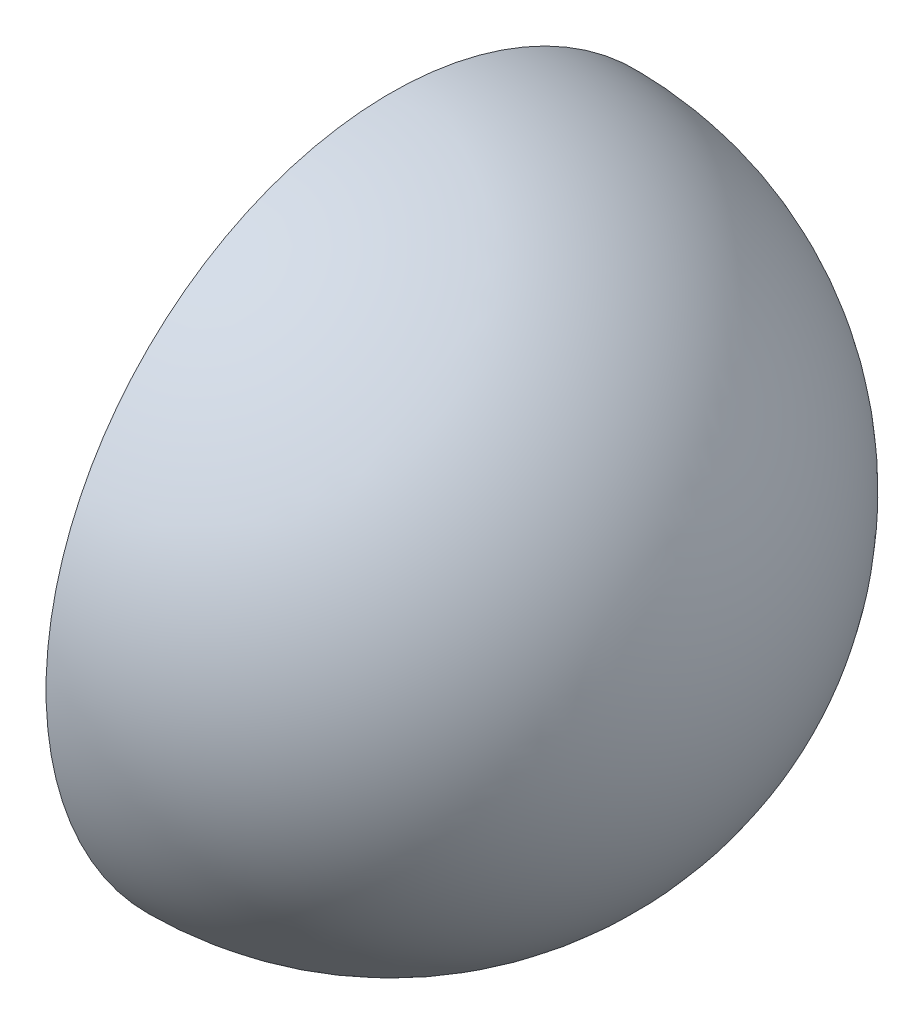
SolidWorks part; units mm, degrees
ref_plane "Front Plane" through (0, 0, 0) normal (1, 0, 0) x (0, 1, 0)
ref_plane "Top Plane" through (0, 0, 0) normal (0, 0, 1) x (0, 1, 0)
ref_plane "Right Plane" through (0, 0, 0) normal (0, 1, 0) x (-1, 0, 0)
sketch "Sketch1" plane through (0, 0, 0) normal (1, 0, 0) x (0, 1, 0)
  line L0 (0, 7.6158) -> (0, -8.9426) construction
  line L1 (0, 6) -> (0, -6)
  arc A0 (0, -6) -> (0, 6) centre (0, 0) ccw
  dimension "D1" = 12
revolve "Revolve3" add sketch "Sketch1" angle 180 about L0
